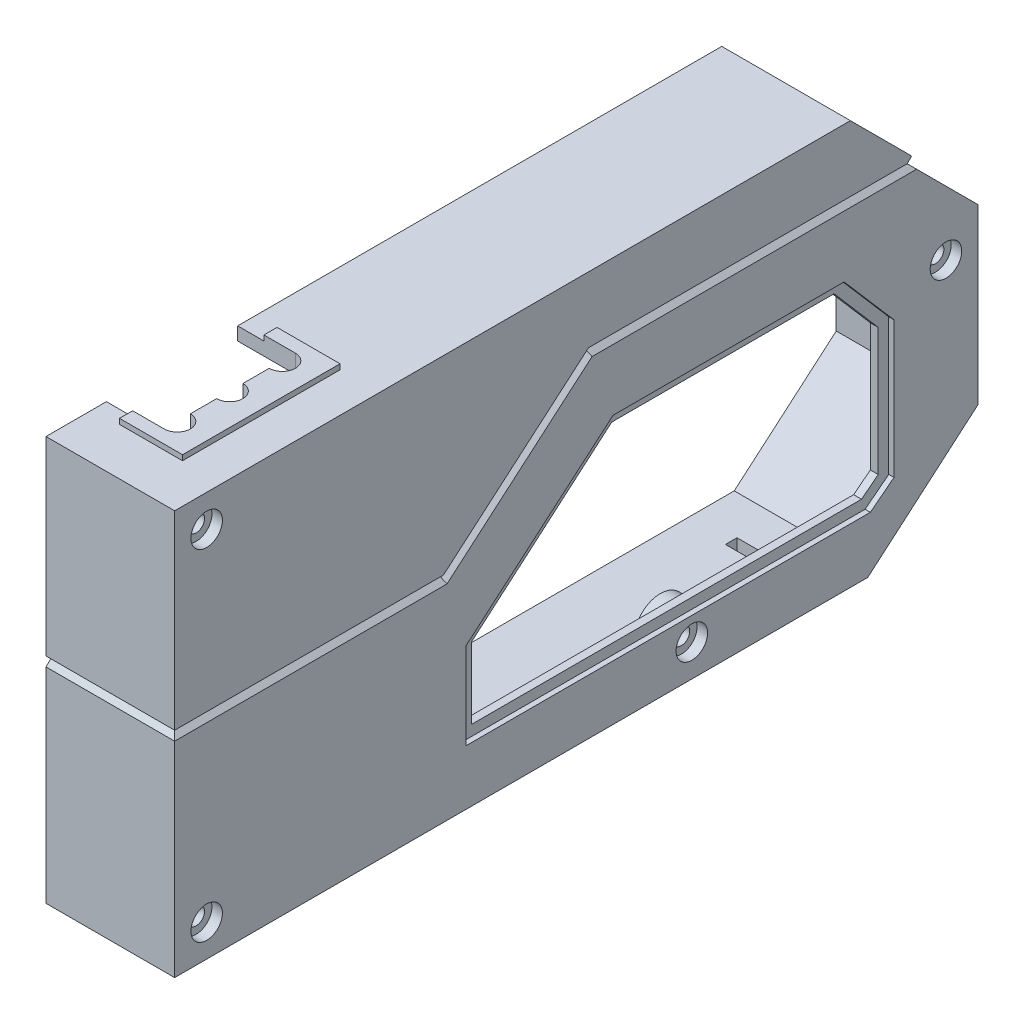
SolidWorks part; units mm, degrees
ref_plane "Front Plane" through (0, 0, 0) normal (0, 0, 1) x (1, 0, 0)
ref_plane "Top Plane" through (0, 0, 0) normal (0, 1, 0) x (1, 0, 0)
ref_plane "Right Plane" through (0, 0, 0) normal (1, 0, 0) x (0, 0, -1)
sketch "Sketch1" plane through (0, 0, 0) normal (1, 0, 0) x (0, 0, -1)
  line L0 (0, 0) -> (0, 77)
  line L1 (0, 77) -> (127, 77)
  line L2 (127, 77) -> (153, 51)
  line L3 (153, 51) -> (153, 18)
  line L4 (153, 18) -> (132, 0)
  line L5 (132, 0) -> (0, 0)
  dimension "D1" = 132
  dimension "D2" = 77
  dimension "D3" = 26
  dimension "D4" = 26
  dimension "D5" = 153
  dimension "D6" = 18
extrude "Base" add sketch "Sketch1" along normal blind 2.5
sketch "Sketch11" plane through (0, 0, 0) normal (-1, 0, 0) x (0, 0, 1)
  line L12 (-131.0752, 2.5) -> (-2.5, 2.5)
  line L13 (-2.5, 2.5) -> (-2.5, 74.5)
  line L14 (-2.5, 74.5) -> (-125.9645, 74.5)
  line L15 (-125.9645, 74.5) -> (-150.5, 49.9645)
  line L16 (-150.5, 49.9645) -> (-150.5, 19.1498)
  line L17 (-150.5, 19.1498) -> (-131.0752, 2.5)
  line L18 (-131.0752, 2.5) -> (-2.5, 2.5)
  line L19 (-2.5, 2.5) -> (-2.5, 74.5)
  line L20 (-2.5, 74.5) -> (-125.9645, 74.5)
  line L21 (-125.9645, 74.5) -> (-150.5, 49.9645)
  line L22 (-150.5, 49.9645) -> (-150.5, 19.1498)
  line L23 (-150.5, 19.1498) -> (-131.0752, 2.5)
  line M7 (-132, 0) -> (0, 0)
  line M8 (0, 0) -> (0, 77)
  line M9 (0, 77) -> (-127, 77)
  line M10 (-127, 77) -> (-153, 51)
  line M11 (-153, 51) -> (-153, 18)
  line M12 (-153, 18) -> (-132, 0)
  dimension "D1" = 2.5
extrude "Boss-Extrude6" add sketch "Sketch11" along normal blind 22 contours L23 L22 L21 L20 L19 L18 M12 M7 M8 M9 M10 M11 region at (0, 10.3005, -141.3853)
ref_plane "Middle" through (-11, 0, 0) normal (1, 0, 0) x (0, 0, -1)
sketch "Sketch17" plane through (0, 77, 0) normal (0, 1, 0) x (1, 0, 0)
  line L5 (-11, -42.35) -> (-11, 42.35) construction
  line L6 (-5, 39) -> (-17, 39)
  line L7 (-5, 39) -> (-5, 9)
  line L8 (-5, 9) -> (-17, 9)
  line L9 (-17, 39) -> (-17, 9)
  line L10 (-5, 39) -> (-17, 9) construction
  line L11 (-5, 9) -> (-17, 39) construction
  line L12 (2.5, 0) -> (-22, 0) construction
  point P0 (-11, 24)
  dimension "D1" = 12
  dimension "D2" = 30
  dimension "D3" = 24
extrude "Boss-Extrude8" add sketch "Sketch17" along normal blind 1
sketch "Sketch13" plane through (0, 78, 0) normal (0, 1, 0) x (1, 0, 0)
  line L0 (-22, 11.5) -> (-11, 11.5)
  line L1 (-22, 0) -> (-22, 127) construction
  line L2 (-11, 16.5) -> (-11, 21.5)
  line L3 (-11, 26.5) -> (-11, 31.5)
  line L4 (-11, 36.5) -> (-22, 36.5)
  line L5 (-22, 36.5) -> (-22, 11.5)
  line L6 (-5, 9) -> (-5, 39) construction
  line L7 (-11, -42.35) -> (-11, 42.35) construction
  arc A0 (-11, 11.5) -> (-11, 16.5) centre (-11, 14) ccw
  arc A1 (-11, 21.5) -> (-11, 26.5) centre (-11, 24) ccw
  arc A2 (-11, 31.5) -> (-11, 36.5) centre (-11, 34) ccw
  point P9 (-5, 24)
  dimension "D1" = 5
  dimension "D4" = 10
  dimension "D5" = 10
extrude "Cut-Extrude2" cut sketch "Sketch13" against normal up to next
sketch "Sketch19" plane through (2.5, 0, 0) normal (1, 0, 0) x (0, 0, -1)
  line L0 (127, 77) -> (128.6971, 77)
  line L1 (128.6971, 77) -> (140.3643, 65.3327)
  line L2 (140.3643, 65.3327) -> (139.5158, 64.4842)
  line L3 (153, 51) -> (127, 77) construction
  line L4 (139.5158, 64.4842) -> (127, 77)
  dimension "D1" = 1.2
  dimension "D2" = 16.5
extrude "Boss-Extrude9" add sketch "Sketch19" against normal up to vertex (24.5 mm away) up to point (-22, 77, -127)
sketch "Sketch20" plane through (0, 102.8485, -102.8485) normal (0, 0.7071, -0.7071) x (-1, 0, 0)
  line L1 (11, 42.35) -> (11, -42.35) construction
  line L2 (2.5, -53.0553) -> (19.5, -53.0553)
  line L3 (2.5, -53.0553) -> (2.5, -44.5553)
  line L4 (2.5, -44.5553) -> (19.5, -44.5553)
  line L5 (19.5, -53.0553) -> (19.5, -44.5553)
  line L6 (2.5, -53.0553) -> (19.5, -44.5553) construction
  line L7 (2.5, -44.5553) -> (19.5, -53.0553) construction
  line L8 (-2.5, -53.0553) -> (-2.5, -36.5553) construction
  line L9 (22, -36.5553) -> (-2.5, -36.5553) construction
  line L10 (22, -53.0553) -> (-2.5, -53.0553) construction
  point P2 (11, -48.8053)
  dimension "D1" = 5
  dimension "D2" = 8
extrude "Cut-Extrude5" cut sketch "Sketch20" against normal up to vertex (1.2 mm away) up to point (2.5, 64.4842, -139.5158)
sketch "Sketch21" plane through (0, 102, -102) normal (0, 0.7071, -0.7071) x (-1, 0, 0)
  line L0 (11, 48.4) -> (11, -48.4) construction
  line L1 (19.5, -44.5553) -> (2.5, -44.5553) construction
  line L2 (11, -48.0053) -> (22, -48.0053)
  line L3 (22, -48.0053) -> (22, -53.1053)
  line L4 (22, -53.0553) -> (22, -72.1249) construction
  line L5 (11, -53.1053) -> (22, -53.1053)
  line L6 (22, 44.5477) -> (22, 46.3155) construction
  arc A0 (11, -48.0053) -> (11, -53.1053) centre (11, -50.5553) ccw
  dimension "D1" = 5.1
  dimension "D2" = 6
extrude "Cut-Extrude6" cut sketch "Sketch21" against normal mid plane 10
sketch "Sketch28" plane through (2.5, 0, 0) normal (1, 0, 0) x (0, 0, -1)
  circle A0 centre (6.1, 70.9) radius 5
  circle A1 centre (146.9, 44.9) radius 5
  circle A2 centre (98.5, 6.1) radius 5
  circle A3 centre (6.1, 6.1) radius 5
  dimension "D9" = 10
  dimension "D1" = 6.1
  dimension "D2" = 6.1
  dimension "D3" = 70.9
  dimension "D4" = 6.1
  dimension "D5" = 98.5
  dimension "D6" = 6.1
  dimension "D7" = 44.9
  dimension "D8" = 146.9
extrude "Boss-Extrude11" add sketch "Sketch28" against normal blind 6
sketch "Sketch29" plane through (2.5, 0, 0) normal (1, 0, 0) x (0, 0, -1)
  circle A0 centre (6.1, 70.9) radius 3
  circle A1 centre (146.9, 44.9) radius 3
  circle A2 centre (98.5, 6.1) radius 3
  circle A3 centre (6.1, 6.1) radius 3
  dimension "D1" = 6
extrude "Cut-Extrude11" cut sketch "Sketch29" against normal blind 2
sketch "Sketch30" plane through (0.5, 0, 0) normal (1, 0, 0) x (0, 0, -1)
  circle A0 centre (6.1, 70.9) radius 1.6
  circle A1 centre (6.1, 6.1) radius 1.6
  circle A2 centre (146.9, 44.9) radius 1.6
  circle A3 centre (98.5, 6.1) radius 1.6
  dimension "D1" = 3.2
extrude "Cut-Extrude12" cut sketch "Sketch30" against normal up to next
sketch "Sketch31" plane through (0, 0, 0) normal (-1, 0, 0) x (0, 0, 1)
  line L1 (-14.5, 47.5) -> (-4.5, 47.5)
  line L2 (-14.5, 47.5) -> (-14.5, 22.5)
  line L3 (-14.5, 22.5) -> (-4.5, 22.5)
  line L4 (-4.5, 47.5) -> (-4.5, 22.5)
  line L5 (-14.5, 47.5) -> (-4.5, 22.5) construction
  line L6 (-14.5, 22.5) -> (-4.5, 47.5) construction
  point P0 (-9.5, 35)
  dimension "D1" = 9.5
  dimension "D2" = 35
  dimension "D3" = 25
  dimension "D4" = 10
extrude "Battery_Support" add sketch "Sketch31" along normal blind 3.4
sketch "Sketch25" plane through (2.5, 0, 0) normal (1, 0, 0) x (0, 0, -1)
  line L0 (55.5, 10.5) -> (132.5, 10.5)
  line L1 (132.5, 10.5) -> (137, 14)
  line L2 (137, 14) -> (137, 40)
  line L3 (137, 40) -> (127.5, 51)
  line L4 (127.5, 51) -> (83.5, 51)
  line L5 (83.5, 51) -> (55.5, 27)
  line L6 (55.5, 27) -> (55.5, 10.5)
  dimension "D1" = 77
  dimension "D2" = 4.5
  dimension "D3" = 3.5
  dimension "D4" = 72
  dimension "D5" = 26
  dimension "D6" = 10.5
  dimension "D7" = 55.5
  dimension "D8" = 40.5
  dimension "D9" = 28
  dimension "D10" = 16.5
extrude "Cut-Extrude9" cut sketch "Sketch25" against normal blind 1
sketch "Sketch26" plane through (1.5, 0, 0) normal (1, 0, 0) x (0, 0, -1)
  line L14 (57.5, 26.0801) -> (57.5, 12.5)
  line L15 (57.5, 12.5) -> (131.8138, 12.5)
  line L16 (131.8138, 12.5) -> (135, 14.9782)
  line L17 (135, 14.9782) -> (135, 39.2559)
  line L18 (135, 39.2559) -> (126.5846, 49)
  line L19 (126.5846, 49) -> (84.2398, 49)
  line L20 (84.2398, 49) -> (57.5, 26.0801)
  line L21 (57.5, 26.0801) -> (57.5, 12.5)
  line L22 (57.5, 12.5) -> (131.8138, 12.5)
  line L23 (131.8138, 12.5) -> (135, 14.9782)
  line L24 (135, 14.9782) -> (135, 39.2559)
  line L25 (135, 39.2559) -> (126.5846, 49)
  line L26 (126.5846, 49) -> (84.2398, 49)
  line L27 (84.2398, 49) -> (57.5, 26.0801)
  dimension "D1" = 2
extrude "Cut-Extrude10" cut sketch "Sketch26" against normal up to next
sketch "Sketch32" plane through (2.5, 0, 0) normal (1, 0, 0) x (0, 0, -1)
  line L0 (144.5158, 63.6842) -> (79.1216, 63.6842)
  line L1 (79.1216, 63.6842) -> (51.49, 40)
  line L2 (51.49, 40) -> (0, 40)
  line L3 (0, 77) -> (0, 0) construction
  line L4 (83.5, 51) -> (55.5, 27) construction
  line L5 (144.5158, 63.6842) -> (144.5158, 64.4842)
  line L6 (144.5158, 64.4842) -> (78.8257, 64.4842)
  line L7 (78.8257, 64.4842) -> (51.1941, 40.8)
  line L8 (51.1941, 40.8) -> (0, 40.8)
  line L9 (0, 40.8) -> (0, 40)
  dimension "D1" = 0.8
  dimension "D2" = 0.8
  dimension "D3" = 0.8
  dimension "D4" = 5
  dimension "D5" = 12.48
  dimension "D6" = 40
extrude "Cut-Extrude13" cut sketch "Sketch32" against normal blind 1
sketch "Sketch33" plane through (0, 0, 0) normal (0, 0, 1) x (1, 0, 0)
  line L0 (-22, 0) -> (-22, 77) construction
  line L1 (1.5, 40.8) -> (-22, 40.8)
  line L2 (1.5, 40.8) -> (1.5, 40)
  line L3 (1.5, 40) -> (-22, 40)
  line L4 (-22, 40.8) -> (-22, 40)
extrude "Cut-Extrude14" cut sketch "Sketch33" against normal blind 1
chamfer "Chamfer1" distance 1 angle 45 4 edges at (-9.75, 40, 0) (2.5, 40, -25.745) (2.5, 51.8421, -65.3058) (2.5, 63.6842, -109.7187)
sketch "Sketch23" plane through (0, 0, 0) normal (0, -1, 0) x (1, 0, 0)
  line L0 (-11, -42.9) -> (-11, 42.9) construction
  line L2 (-8, -10.5) -> (-14, -10.5)
  line L3 (-8, -10.5) -> (-8, -8.3)
  line L4 (-8, -123.6) -> (-14, -123.6)
  line L5 (-5.5, -10.5) -> (-16.5, -10.5)
  line L6 (-5.5, -10.5) -> (-5.5, -60.5)
  line L7 (-5.5, -60.5) -> (-16.5, -60.5)
  line L8 (-16.5, -10.5) -> (-16.5, -60.5)
  line L9 (-8, -123.6) -> (-8, -121.4)
  line L10 (-8, -121.4) -> (-14, -121.4)
  line L11 (-8, -8.3) -> (-14, -8.3)
  line L12 (-14, -10.5) -> (-14, -8.3)
  line L13 (-8, -10.5) -> (-14, -8.3) construction
  line L14 (-8, -8.3) -> (-14, -10.5) construction
  line L15 (-14, -123.6) -> (-14, -121.4)
  line L16 (-8, -123.6) -> (-14, -121.4) construction
  line L17 (-8, -121.4) -> (-14, -123.6) construction
  point P4 (-11, -10.5)
  point P7 (-11, -9.4)
  point P15 (-11, -122.5)
  dimension "D1" = 10.5
  dimension "D2" = 11
  dimension "D3" = 6
  dimension "D4" = 50
  dimension "D5" = 2.2
  dimension "D6" = 6
  dimension "D7" = 2.2
  dimension "D8" = 122.5
extrude "Cut-Extrude7" cut sketch "Sketch23" against normal up to next contours L5 L8 L7 L6 L2 | L12 L2 L3 L11 | L15 L4 L9 L10 region at (-11, 0, -35.5) region at (-11, 0, -9.4) region at (-11, 0, -122.5)
equation "\"D5@Sketch13\"=\"D4@Sketch13\""
equation "\"D2@Sketch32\"=\"D1@Sketch32\""
equation "\"D3@Sketch32\"=\"D1@Sketch32\""
